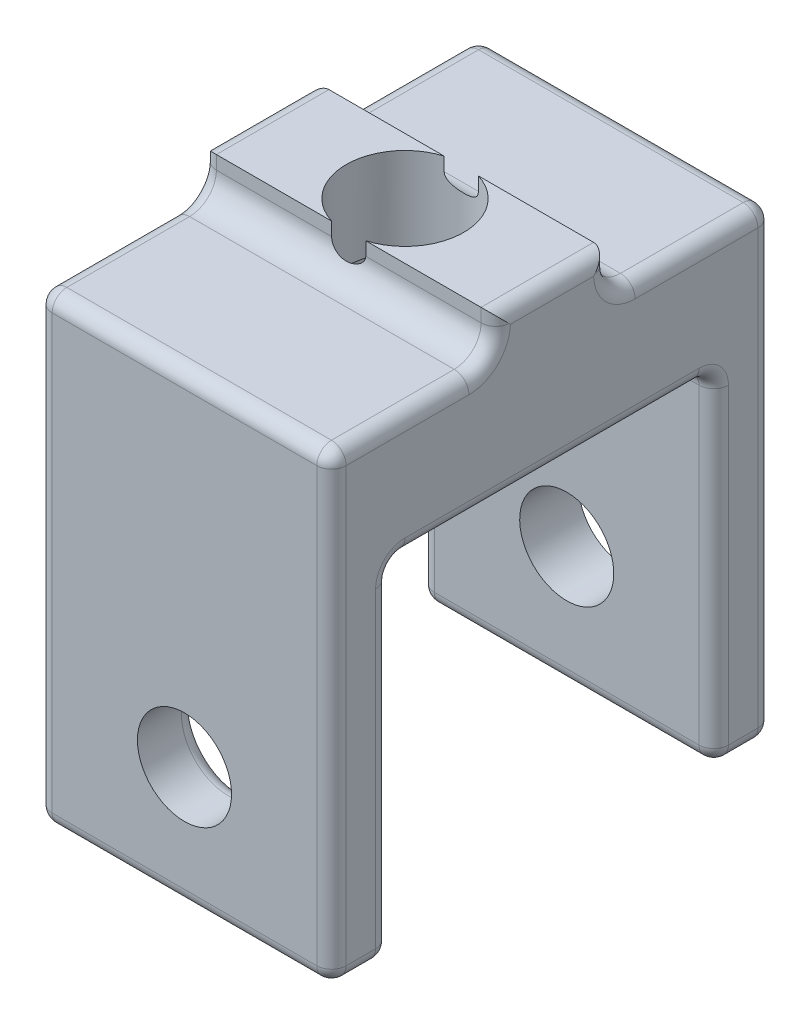
SolidWorks part; units mm, degrees
ref_plane "Front Plane" through (0, 0, 0) normal (0, 0, 1) x (1, 0, 0)
ref_plane "Top Plane" through (0, 0, 0) normal (0, 1, 0) x (1, 0, 0)
ref_plane "Right Plane" through (0, 0, 0) normal (1, 0, 0) x (0, 0, -1)
sketch "Sketch1" plane through (0, 0, 0) normal (1, 0, 0) x (0, 0, -1)
  line L5 (-10.692, -23.4298) -> (-10.692, -19.3) construction
  line L6 (-25.692, -19.3) -> (4.308, -19.3)
  line L10 (-10.692, -16.5596) -> (-10.692, -27.5596) construction
  line L98 (-25.692, -19.3) -> (-25.692, -27.5596)
  line L99 (-16.3445, -19.3) -> (-5.0394, -19.3)
  line L100 (-6.8642, -16.5596) -> (-14.5197, -16.5596)
  line L104 (-14.5197, -17.4752) -> (-14.5197, -16.5596)
  line L105 (-6.8642, -16.5596) -> (-6.8642, -17.4752)
  line L106 (-25.692, -27.5596) -> (4.308, -27.5596)
  line L107 (4.308, -19.3) -> (4.308, -27.5596)
  line L108 (-25.692, -19.3) -> (4.308, -27.5596) construction
  line L109 (-25.692, -27.5596) -> (4.308, -19.3) construction
  arc A84 (-14.5197, -17.4752) -> (-16.3445, -19.3) centre (-16.3445, -17.4752) cw
  arc A85 (-6.8642, -17.4752) -> (-5.0394, -19.3) centre (-5.0394, -17.4752) ccw
  point P0 (-10.692, -23.4298)
  point P8 (-12.5579, -19.3)
  dimension "D2" = 1.8248
  dimension "D3" = 1.8248
  dimension "D1" = 7.6555
  dimension "D4" = 11
  dimension "D5" = 30
extrude "Boss-Extrude1" add sketch "Sketch1" along normal blind 20 contours A85 L105 L100 L104 A84 L6 | L6 L107 L106 L98 region at (0, -17.9912, 10.692)
sketch "Sketch2" plane through (0, -27.5596, 0) normal (0, -1, 0) x (1, 0, 0)
  line L0 (0, 10.692) -> (20, 10.692) construction
  line L1 (0, 25.692) -> (0, -4.308) construction
  line L2 (20, 25.692) -> (20, -4.308) construction
  circle A0 centre (10, 10.692) radius 4
  circle A1 centre (10, 10.692) radius 8.5
  dimension "D1" = 8
  dimension "D2" = 17
extrude "Cut-Extrude1" cut sketch "Sketch2" against normal blind 20 contours A0
extrude "Cut-Extrude2" cut sketch "Sketch2<3>" against normal blind 5
sketch "Sketch2<3>" plane through (0, -27.5596, 0) normal (0, -1, 0) x (1, 0, 0) same geometry as "Sketch2"
sketch "Sketch3" plane through (0, 0, -4.308) normal (0, 0, -1) x (-1, 0, 0)
  line L0 (-10, -27.5596) -> (-10, -42.5596) construction
  line L1 (-20, -27.5596) -> (0, -27.5596)
  line L2 (-20, -27.5596) -> (-20, -50.7596)
  line L3 (-20, -50.7596) -> (0, -50.7596)
  line L4 (0, -27.5596) -> (0, -50.7596)
  line L5 (-10, -45.7596) -> (-10, -50.7596) construction
  line L6 (0, -19.3) -> (0, -27.5596) construction
  circle A0 centre (-10, -42.5596) radius 3.2
  circle A1 centre (-10, -42.5596) radius 5
  line M11 (-20, -27.5596) -> (0, -27.5596)
  dimension "D3" = 6.4
  dimension "D5" = 10
  dimension "D1" = 15
  dimension "D2" = 5
  dimension "D4" = 23.2
extrude "Boss-Extrude2" add sketch "Sketch3" against normal blind 4 contours L4 L2 L3 A1 M11 | A1 A0 region at (10, -27.8659, -4.308) region at (14.8586, -42.5596, -4.308)
extrude "Boss-Extrude3" add sketch "Sketch3<3>" along normal blind 4 from surface contours L4 L2 L3 A1 M11 | A1 A0 region at (10, -27.8659, -4.308) region at (14.8586, -42.5596, -4.308) starting at face at (10, -23.4298, 25.692)
sketch "Sketch3<3>" plane through (0, 0, -4.308) normal (0, 0, -1) x (-1, 0, 0) same geometry as "Sketch3"
fillet "Fillet1" radius 1 33 edges at (10, -50.7596, -0.308) (10, -27.5596, -0.308) (20, -19.3, 0.3657) (20, -35.0298, -4.308) (20, -50.7596, -2.308) (20, -39.1596, -0.308) (20, -27.5596, 10.692) (20, -35.0298, 25.692) (20, -19.3, 21.0182) (20, -18.7655, 15.0542) (20, -16.5596, 10.692) (20, -18.7655, 6.3297) (0, -16.5596, 10.692) (0, -18.7655, 15.0542) (0, -19.3, 21.0182) (0, -35.0298, 25.692) (0, -27.5596, 10.692) (0, -39.1596, -0.308) (0, -50.7596, -2.308) (0, -35.0298, -4.308) (0, -19.3, 0.3657) (0, -18.7655, 6.3297) (20, -50.7596, 23.692) (0, -50.7596, 23.692) (10, -50.7596, 25.692) (10, -39.3596, 21.692) (20, -39.1596, 21.692) (10, -27.5596, 21.692) (0, -39.1596, 21.692) (10, -50.7596, 21.692) (10, -19.3, 25.692) (10, -19.3, -4.308) (10, -50.7596, -4.308)
